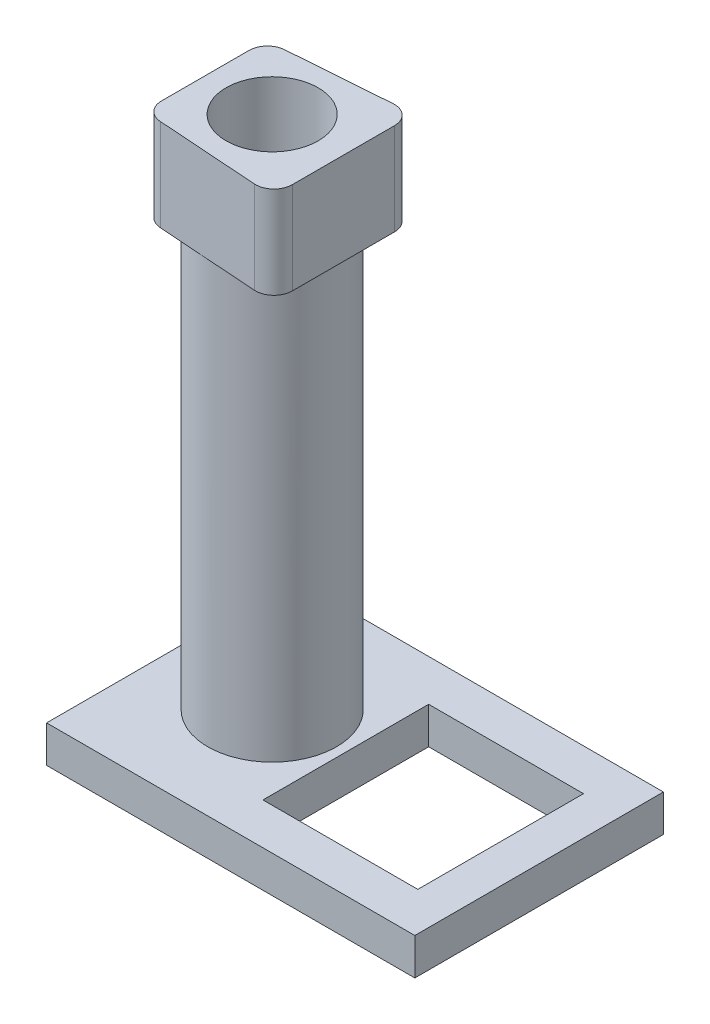
SolidWorks part; units mm, degrees
ref_plane "Спереди" through (0, 0, 0) normal (0, 0, 1) x (1, 0, 0)
ref_plane "Сверху" through (0, 0, 0) normal (0, 1, 0) x (1, 0, 0)
ref_plane "Справа" through (0, 0, 0) normal (1, 0, 0) x (0, 0, -1)
sketch "Эскиз1" plane through (0, 0, 0) normal (0, 1, 0) x (1, 0, 0)
  line L0 (-12.3747, 0) -> (66.873, 0) construction
  line L1 (-55, -67.5) -> (145, -67.5)
  line L2 (-55, -67.5) -> (-55, 67.5)
  line L3 (-55, 67.5) -> (145, 67.5)
  line L4 (145, -67.5) -> (145, 67.5)
  line L5 (-55, -67.5) -> (145, 67.5) construction
  line L6 (-55, 67.5) -> (145, -67.5) construction
  line L7 (40, -45) -> (124.1121, -45)
  line L8 (40, -45) -> (40, 45)
  line L9 (40, 45) -> (124.1121, 45)
  line L10 (124.1121, -45) -> (124.1121, 45)
  point P0 (45, 0)
  point P9 (0, 0)
  point P10 (40, 0)
extrude "Бобышка-Вытянуть1" add sketch "Эскиз1" along normal blind 20
sketch "Эскиз3" plane through (0, 20, 0) normal (0, 1, 0) x (1, 0, 0)
  circle A0 centre (0, 0) radius 35
extrude "Вытянуть-Тонкостенный1" add sketch "Эскиз3" along normal blind 230 thin thin type one direction reverse wall 10
sketch "Эскиз4" plane through (0, 250, 0) normal (0, 1, 0) x (1, 0, 0)
  line L1 (38.567, 27.8805) -> (38.567, -27.6017)
  line L2 (27.8707, -37.5774) -> (-27.0249, -33.7454)
  line L3 (-27.0732, 33.7534) -> (27.8224, 37.8528)
  line L4 (-36.3285, -23.7697) -> (-36.3285, 23.7812)
  arc A0 (-36.3285, -23.7697) -> (-27.0249, -33.7454) centre (-26.3285, -23.7697) ccw
  arc A1 (38.567, -27.6017) -> (27.8707, -37.5774) centre (28.567, -27.6017) cw
  arc A2 (27.8224, 37.8528) -> (38.567, 27.8805) centre (28.567, 27.8805) cw
  arc A3 (-36.3285, 23.7812) -> (-27.0732, 33.7534) centre (-26.3285, 23.7812) cw
  circle A4 centre (0, 0) radius 25
  dimension "D1" = 10
  dimension "D2" = 10
extrude "Бобышка-Вытянуть2" add sketch "Эскиз4" along normal blind 50
